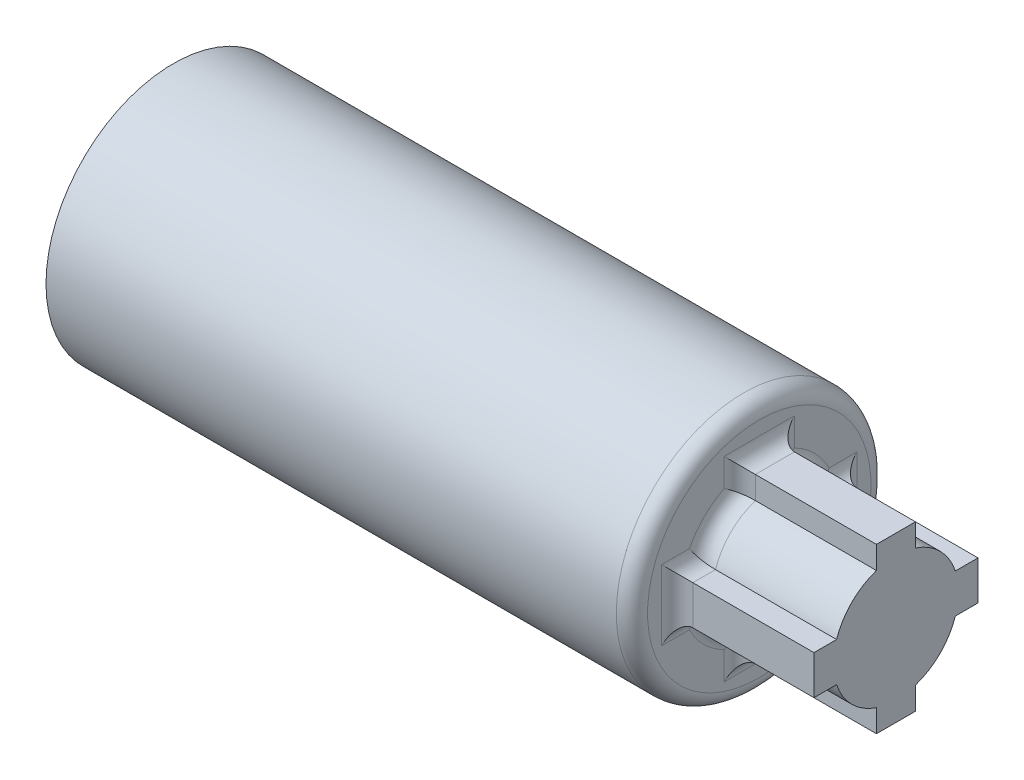
SolidWorks part; units mm, degrees
material "ABS"
ref_plane "Front Plane" through (0, 0, 0) normal (0, 0, 1) x (1, 0, 0)
ref_plane "Top Plane" through (0, 0, 0) normal (0, 1, 0) x (1, 0, 0)
ref_plane "Right Plane" through (0, 0, 0) normal (1, 0, 0) x (0, 0, -1)
sketch "Sketch1" plane through (9.0729, 0, 0) normal (-1, 0, 0) x (0, 0, 1)
  line L0 (-22.5649, -14.994) -> (-21.5649, -14.994)
  line L1 (-24.1649, -19.194) -> (-19.9649, -19.194) construction
  line L2 (-24.1649, -19.194) -> (-24.1649, -14.994) construction
  line L3 (-24.1649, -14.994) -> (-19.9649, -14.994) construction
  line L4 (-19.9649, -19.194) -> (-19.9649, -14.994) construction
  line L5 (-24.1649, -19.194) -> (-19.9649, -14.994) construction
  line L6 (-24.1649, -14.994) -> (-19.9649, -19.194) construction
  line L7 (-21.5649, -14.994) -> (-21.5649, -15.5742)
  line L8 (-22.5649, -14.994) -> (-22.5649, -15.5742)
  line L9 (-19.9649, -16.594) -> (-20.545, -16.594)
  line L10 (-19.9649, -16.594) -> (-19.9649, -17.594)
  line L11 (-19.9649, -17.594) -> (-20.545, -17.594)
  line L12 (-21.5649, -19.194) -> (-21.5649, -18.6139)
  line L13 (-21.5649, -19.194) -> (-22.5649, -19.194)
  line L14 (-22.5649, -19.194) -> (-22.5649, -18.6139)
  line L15 (-24.1649, -17.594) -> (-23.5848, -17.594)
  line L16 (-24.1649, -17.594) -> (-24.1649, -16.594)
  line L17 (-24.1649, -16.594) -> (-23.5848, -16.594)
  line L18 (-24.0149, -16.744) -> (-23.472, -16.744)
  line L19 (-22.4149, -15.144) -> (-22.4149, -15.6869)
  line L20 (-22.4149, -15.144) -> (-21.7149, -15.144)
  line L21 (-21.7149, -15.144) -> (-21.7149, -15.6869)
  line L22 (-20.1149, -16.744) -> (-20.6578, -16.744)
  line L23 (-20.1149, -16.744) -> (-20.1149, -17.444)
  line L24 (-20.1149, -17.444) -> (-20.6578, -17.444)
  line L25 (-21.7149, -19.044) -> (-21.7149, -18.5012)
  line L26 (-21.7149, -19.044) -> (-22.4149, -19.044)
  line L27 (-22.4149, -19.044) -> (-22.4149, -18.5012)
  line L28 (-24.0149, -17.444) -> (-23.472, -17.444)
  line L29 (-24.0149, -17.444) -> (-24.0149, -16.744)
  line L30 (-20.9989, -49.3667) -> (-16.1659, 14.4506) construction
  line L31 (-20.9989, -49.3667) -> (-16.1659, 14.4506) construction
  line L32 (-23.7116, -18.9751) -> (-20.7202, -19.2016) construction
  line L33 (-23.7521, -19.0723) -> (-20.6949, -19.3038)
  circle A0 centre (-22.0649, -17.094) radius 1.6 construction
  arc A1 (-23.5848, -17.594) -> (-22.5649, -18.6139) centre (-22.0649, -17.094) ccw construction
  arc A2 (-23.5848, -17.594) -> (-22.5649, -18.6139) centre (-22.0649, -17.094) ccw
  arc A3 (-22.5649, -15.5742) -> (-23.5848, -16.594) centre (-22.0649, -17.094) ccw construction
  arc A4 (-22.5649, -15.5742) -> (-23.5848, -16.594) centre (-22.0649, -17.094) ccw
  arc A5 (-20.545, -16.594) -> (-21.5649, -15.5742) centre (-22.0649, -17.094) ccw construction
  arc A6 (-20.545, -16.594) -> (-21.5649, -15.5742) centre (-22.0649, -17.094) ccw
  arc A7 (-21.5649, -18.6139) -> (-20.545, -17.594) centre (-22.0649, -17.094) ccw construction
  arc A8 (-21.5649, -18.6139) -> (-20.545, -17.594) centre (-22.0649, -17.094) ccw
  arc A9 (-22.4149, -15.6869) -> (-23.472, -16.744) centre (-22.0649, -17.094) ccw
  arc A10 (-20.6578, -16.744) -> (-21.7149, -15.6869) centre (-22.0649, -17.094) ccw
  arc A11 (-21.7149, -18.5012) -> (-20.6578, -17.444) centre (-22.0649, -17.094) ccw
  arc A12 (-23.472, -17.444) -> (-22.4149, -18.5012) centre (-22.0649, -17.094) ccw
  arc A13 (-21.8761, -14.6012) -> (-23.7116, -18.9751) centre (-22.0649, -17.094) ccw construction
  arc A14 (-20.7202, -19.2016) -> (-21.8761, -14.6012) centre (-22.0649, -17.094) ccw construction
  arc A15 (-21.8761, -14.6012) -> (-23.7116, -18.9751) centre (-22.0649, -17.094) ccw construction
  arc A16 (-20.7202, -19.2016) -> (-21.8761, -14.6012) centre (-22.0649, -17.094) ccw construction
  arc A17 (-20.6949, -19.3038) -> (-21.8685, -14.5015) centre (-22.0649, -17.094) ccw
  arc A18 (-21.8685, -14.5015) -> (-23.7521, -19.0723) centre (-22.0649, -17.094) ccw
  circle A19 centre (-22.0649, -17.094) radius 3.2593
  point P9 (-22.0649, -14.994)
  point P12 (-22.0649, -14.994)
  point P55 (-18.8056, -17.094)
  dimension "D3" = 4
  dimension "D4" = 0.15
  dimension "D1" = 4.2
  dimension "D2" = 1
  dimension "D5" = 0.1
  dimension "D6" = 0.25
extrude "Boss-Extrude1" add sketch "Sketch1" against normal blind 3.5 contours L11 A8 L12 L13 L14 A2 L15 L16 L17 A4 L8 L0 L7 A6 L9 L10
extrude "Boss-Extrude2" add sketch "Sketch1<3>" along normal blind 1 contours A19
sketch "Sketch1<3>" plane through (9.0729, 0, 0) normal (-1, 0, 0) x (0, 0, 1) same geometry as "Sketch1"
extrude "Boss-Extrude3" add sketch "Sketch1<4>" along normal blind 15 contours A19 A18 A17 L33 L13 | L33 L14 L13 region at (9.0729, -19.1834, -22.4247) region at (9.0729, -17.094, -25.232)
sketch "Sketch1<4>" plane through (9.0729, 0, 0) normal (-1, 0, 0) x (0, 0, 1) same geometry as "Sketch1"
fillet "Fillet1" radius 0.4 17 edges at (9.0729, -20.3533, -22.0649) (9.0729, -18.2254, -23.1963) (9.0729, -17.594, -23.8748) (9.0729, -17.094, -24.1649) (9.0729, -16.594, -23.8748) (9.0729, -15.9627, -23.1963) (9.0729, -15.2841, -22.5649) (9.0729, -14.994, -22.0649) (9.0729, -15.2841, -21.5649) (9.0729, -15.9627, -20.9335) (9.0729, -16.594, -20.255) (9.0729, -17.094, -19.9649) (9.0729, -17.594, -20.255) (9.0729, -18.2254, -20.9335) (9.0729, -18.904, -21.5649) (9.0729, -19.194, -22.0649) (9.0729, -18.904, -22.5649)
